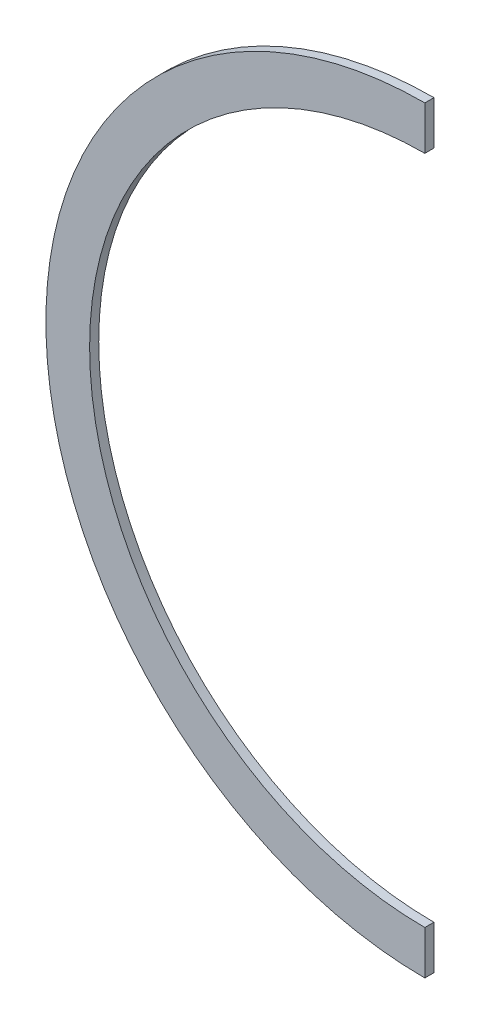
SolidWorks part; units mm, degrees
material "Balsa"
ref_plane "Front Plane" through (0, 0, 0) normal (0, 0, 1) x (1, 0, 0)
ref_plane "Top Plane" through (0, 0, 0) normal (0, 1, 0) x (1, 0, 0)
ref_plane "Right Plane" through (0, 0, 0) normal (1, 0, 0) x (0, 0, -1)
sketch "Sketch2" plane through (0, 0, 0) normal (0, 0, 1) x (1, 0, 0)
  line L0 (0, 0) -> (0, 236.6718) construction
  line L1 (-1.651, 128.5137) -> (-1.651, 121.4017) construction
  line L3 (1.651, 128.5137) -> (1.651, 121.4017) construction
  line L4 (-1.651, 121.4017) -> (1.651, 121.4017) construction
  line L5 (-136.2041, -77.9016) -> (0, 0.7359) construction
  line L6 (-136.2041, -77.9016) -> (0, 0.7359) construction
  line L7 (136.2041, -77.9016) -> (0, 0.7359) construction
  line L8 (136.2041, -77.9016) -> (0, 0.7359) construction
  line L9 (-116.9741, -64.8927) -> (-110.0155, -60.8752) construction
  line L10 (-115.4036, -67.7988) -> (-108.3645, -63.7348) construction
  line L11 (-110.0155, -60.8752) -> (-108.3645, -63.7348) construction
  line L12 (-117.55, -65.2252) -> (-116.9741, -64.8927) construction
  line L13 (-115.899, -68.0849) -> (-115.4036, -67.7988) construction
  line L14 (115.4036, -67.7988) -> (109.2442, -64.2427) construction
  line L15 (110.8952, -61.3831) -> (109.2442, -64.2427) construction
  line L16 (116.9741, -64.8927) -> (110.8952, -61.3831) construction
  arc A0 (-1.651, 128.5137) -> (-116.9741, -64.8927) centre (0, -3.556) ccw
  arc A1 (0.0665, 128.1531) -> (63.0696, -118.8475) centre (0, -3.3993) ccw construction
  circle A2 centre (0, -3.556) radius 116.84
  arc A3 (63.0696, -118.8475) -> (0.0665, 128.1531) centre (0, -3.3993) ccw construction
  arc A4 (0, 128.524) -> (-1.651, 128.5137) centre (0, -3.556) ccw
  circle A5 centre (0, -3.556) radius 132.08 construction
  arc A6 (1.651, 128.5137) -> (0, 128.524) centre (0, -3.556) ccw
  arc A7 (-116.9741, -64.8927) -> (-116.1978, -66.3509) centre (0, -3.556) ccw
  arc A8 (-115.4036, -67.7988) -> (115.4036, -67.7988) centre (0, -3.556) ccw
  arc A9 (-116.1978, -66.3509) -> (-115.4036, -67.7988) centre (0, -3.556) ccw
  arc A10 (115.4036, -67.7988) -> (116.1978, -66.3509) centre (0, -3.556) ccw
  arc A11 (116.9741, -64.8927) -> (1.651, 128.5137) centre (0, -3.556) ccw
  arc A12 (116.1978, -66.3509) -> (116.9741, -64.8927) centre (0, -3.556) ccw
  point P24 (-115.4036, -67.7988)
  dimension "D1" = 3.556
  dimension "D3" = 264.16
  dimension "D2" = 15.24
  dimension "D4" = 3.302
  dimension "D5" = 7.112
  dimension "D6" = 3.302
  dimension "D7" = 8.128
  dimension "D8" = 7.076
extrude "Boss-Extrude1" add sketch "Sketch2" along normal mid plane 3.175
sketch "Sketch3" plane through (0, 0, 0) normal (1, 0, 0) x (0, 0, -1)
  line L1 (-109.3908, 192.564) -> (122.8198, 192.564)
  line L2 (-109.3908, 192.564) -> (-109.3908, -206.3906)
  line L3 (-109.3908, -206.3906) -> (122.8198, -206.3906)
  line L4 (122.8198, 192.564) -> (122.8198, -206.3906)
extrude "Cut-Extrude1" cut sketch "Sketch3" along normal through all
